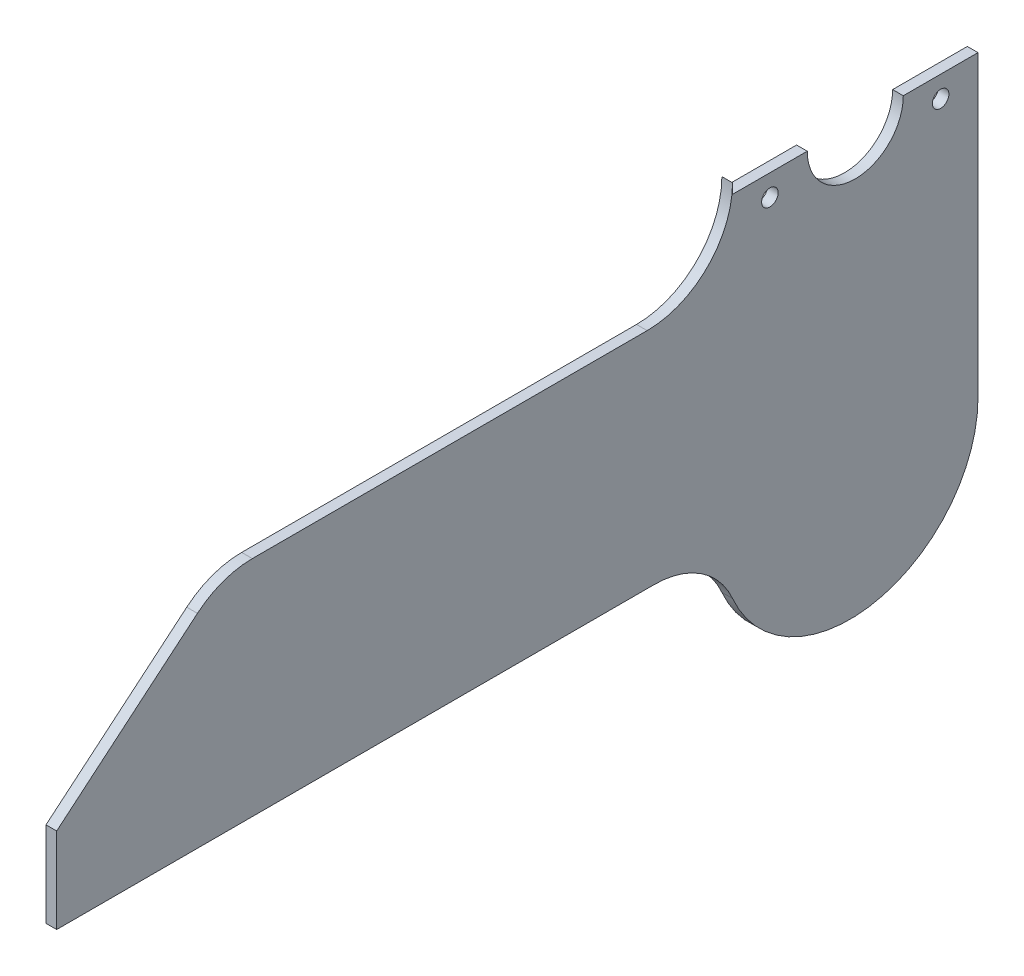
SolidWorks part; units mm, degrees
ref_plane "Front Plane" through (0, 0, 0) normal (0, 0, 1) x (1, 0, 0)
ref_plane "Top Plane" through (0, 0, 0) normal (0, 1, 0) x (1, 0, 0)
ref_plane "Right Plane" through (0, 0, 0) normal (1, 0, 0) x (0, 0, -1)
sketch "Sketch1" plane through (0, 0, 0) normal (1, 0, 0) x (0, 0, -1)
  line L0 (0, -44.45) -> (0, 44.45)
  line L7 (0, 44.45) -> (-22.225, 44.45)
  line L8 (-50.8, 44.45) -> (-73.025, 44.45)
  line L10 (-98.425, 22.0322) -> (-215.9, 22.0322)
  line L13 (-274.1047, -44.45) -> (-96.3047, -44.45)
  line L14 (-274.1047, -44.45) -> (-274.1047, -19.05)
  line L15 (-274.1047, -19.05) -> (-232.2268, 16.0897)
  line L16 (-274.1047, -19.05) -> (0, -19.05) construction
  line L17 (-96.3047, -44.45) -> (0, -44.45) construction
  line L18 (-73.025, 44.45) -> (-73.025, 47.4322)
  arc A2 (-22.225, 44.45) -> (-50.8, 44.45) centre (-36.5125, 44.45) cw
  arc A3 (-73.025, -59.6905) -> (0, -44.45) centre (-38.1029, -44.45) ccw
  arc A4 (-215.9, 22.0322) -> (-232.2268, 16.0897) centre (-215.9, -3.3678) ccw
  arc A5 (-96.3047, -44.45) -> (-73.025, -59.6905) centre (-96.3047, -69.85) cw
  arc A6 (-73.025, 47.4322) -> (-98.425, 22.0322) centre (-98.425, 47.4322) cw
  point P2 (0, 0)
  point P4 (0, 0)
  point P9 (-32.1857, 44.45)
  point P20 (-76.2057, -44.45)
  dimension "D1" = 28.575
  dimension "D4" = 25.4
  dimension "D7" = 25.4
  dimension "D2" = 88.9
  dimension "D3" = 73.025
  dimension "D5" = 117.475
  dimension "D6" = 177.8
  dimension "D8" = 50
extrude "Boss-Extrude1" add sketch "Sketch1" along normal blind 3.175
hole_wizard "#10 (0.1935) Diameter Hole1" positions "Sketch2" profile "Sketch3" hole size "#10" standard "ANSI Inch" end condition through all
sketch "Sketch2" plane through (3.175, 0, 0) normal (1, 0, 0) x (0, 0, -1)
  line L0 (-50.8, 44.45) -> (-73.025, 44.45) construction
  line L1 (-61.9125, 38.1) -> (-11.1125, 38.1) construction
  line L3 (-36.5125, 38.1) -> (-36.5125, 44.45) construction
  point P0 (-61.9125, 38.1)
  point P2 (-11.1125, 38.1)
  dimension "D1" = 50.8
  dimension "D2" = 6.35
sketch "Sketch3" plane through (3.175, 38.1, 61.9125) normal (0, 1, 0) x (0, 0, -1)
  line L0 (0, 0) -> (0, 3.175)
  line L1 (0, 3.175) -> (2.4574, 3.175)
  line L2 (2.4574, 3.175) -> (2.4574, 0)
  line L5 (2.4574, 0) -> (0, 0)
  line L11 (0, -6.35) -> (0, 107.95) construction
  dimension "Thru Hole Dia." = 4.9149
  dimension "Thru Hole Depth" = 3.175
